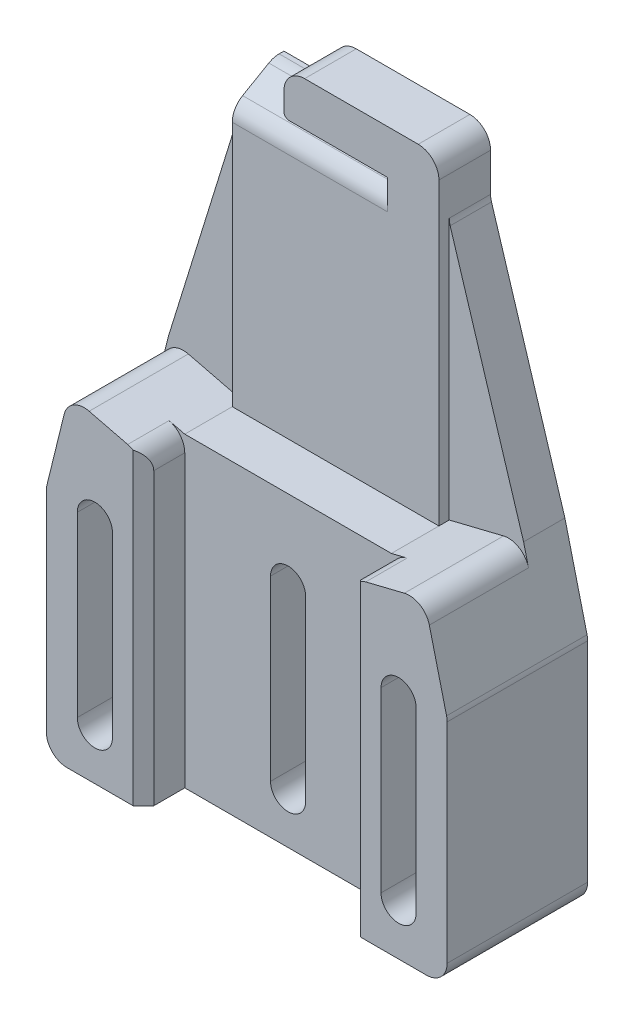
SolidWorks part; units mm, degrees
ref_plane "Front Plane" through (0, 0, 0) normal (0, 0, 1) x (1, 0, 0)
ref_plane "Top Plane" through (0, 0, 0) normal (0, 1, 0) x (1, 0, 0)
ref_plane "Right Plane" through (0, 0, 0) normal (1, 0, 0) x (0, 0, -1)
sketch "Sketch1" plane through (0, 0, 0) normal (0, 0, 1) x (1, 0, 0)
  line L0 (0, 0) -> (10, 0) construction
  line L1 (0, 0) -> (0, 10) construction
  line L2 (16.4, -17.7509) -> (-16.4, -17.7509) construction
  line L3 (16.4, -34.9559) -> (-16.4, -34.9559) construction
  line L4 (-24.9333, -39.6559) -> (24.9333, -39.6559)
  line L5 (-13, -34.9559) -> (-13, -17.7509) construction
  line L6 (-16.4, -17.7509) -> (-16.4, -34.9559) construction
  line L8 (24.9333, -39.6559) -> (10, 21)
  line L9 (10, 21) -> (-10, 21)
  line L10 (-10, 21) -> (-24.9333, -39.6559)
  line L11 (24.9333, -39.6559) -> (-24.9333, -39.6559) construction
  line L12 (-24.9333, -39.6559) -> (-10, 21) construction
  line L13 (10, 21) -> (24.9333, -39.6559) construction
  line L14 (-10, 21) -> (10, 21) construction
  line L18 (5, 15) -> (-5, 15) construction
  line L19 (-5, 16) -> (5, 16) construction
  line L20 (5, 16) -> (5, 15) construction
  line L21 (-5, 15) -> (-5, 16) construction
  line L22 (13, -17.7509) -> (13, -34.9559)
  line L23 (16.4, -34.9559) -> (16.4, -17.7509)
  line L24 (1.7, -17.7509) -> (1.7, -34.9559)
  line L25 (-1.7, -34.9559) -> (-1.7, -17.7509)
  line L26 (-13, -34.9559) -> (-13, -17.7509)
  line L27 (-16.4, -17.7509) -> (-16.4, -34.9559)
  line L29 (-16.4, -34.9559) -> (-16.4, -17.7509)
  line L30 (-13, -17.7509) -> (-13, -34.9559)
  line L31 (16.4, -17.7509) -> (16.4, -34.9559)
  line L32 (13, -34.9559) -> (13, -17.7509)
  line L33 (16.4, -34.9559) -> (16.4, -17.7509) construction
  line L34 (13, -17.7509) -> (13, -34.9559) construction
  line L36 (-1.7, -34.9559) -> (-1.7, -17.7509) construction
  line L37 (1.7, -17.7509) -> (1.7, -34.9559) construction
  line L38 (-5, 16) -> (5, 16) construction
  line L39 (5, 15) -> (-5, 15) construction
  line L40 (5, 16) -> (5, 15) construction
  line L41 (-5, 15) -> (-5, 16) construction
  circle A0 centre (0, 0) radius 10 construction
  circle A1 centre (0, 0) radius 10 construction
  circle A3 centre (0, 72.5) radius 82.5 construction
  arc A13 (16.4, -17.7509) -> (13, -17.7509) centre (14.7, -17.7509) ccw
  arc A14 (13, -34.9559) -> (16.4, -34.9559) centre (14.7, -34.9559) ccw
  arc A15 (-1.7, -34.9559) -> (1.7, -34.9559) centre (0, -34.9559) ccw
  arc A16 (1.7, -17.7509) -> (-1.7, -17.7509) centre (0, -17.7509) ccw
  arc A17 (-16.4, -34.9559) -> (-13, -34.9559) centre (-14.7, -34.9559) ccw
  arc A18 (-13, -17.7509) -> (-16.4, -17.7509) centre (-14.7, -17.7509) ccw
  arc A23 (-13, -34.9559) -> (-16.4, -34.9559) centre (-14.7, -34.9559) cw
  arc A24 (-16.4, -17.7509) -> (-13, -17.7509) centre (-14.7, -17.7509) cw
  arc A25 (13, -17.7509) -> (16.4, -17.7509) centre (14.7, -17.7509) cw
  arc A26 (16.4, -34.9559) -> (13, -34.9559) centre (14.7, -34.9559) cw
  arc A28 (-16.4, -34.9559) -> (-13, -34.9559) centre (-14.7, -34.9559) ccw construction
  arc A29 (13, -34.9559) -> (16.4, -34.9559) centre (14.7, -34.9559) ccw construction
  arc A30 (16.4, -17.7509) -> (13, -17.7509) centre (14.7, -17.7509) ccw construction
  arc A31 (-13, -17.7509) -> (-16.4, -17.7509) centre (-14.7, -17.7509) ccw construction
  arc A32 (1.7, -17.7509) -> (-1.7, -17.7509) centre (0, -17.7509) ccw construction
  arc A33 (-1.7, -34.9559) -> (1.7, -34.9559) centre (0, -34.9559) ccw construction
  circle A34 centre (0, 72.5) radius 82.5 construction
  dimension "D1" = 20
sketch "Sketch2" plane through (0, 0, 0) normal (0, 0, 1) x (1, 0, 0)
  line L0 (10, 21) -> (24.9333, -39.6559) construction
  line L1 (-24.9333, -39.6559) -> (24.9333, -39.6559) construction
  line L2 (-24.9333, -39.6559) -> (-10, 21) construction
  line L3 (-10, 21) -> (10, 21) construction
  line L4 (10, 21) -> (24.9333, -39.6559) construction
  line L5 (24.9333, -39.6559) -> (-24.9333, -39.6559) construction
  line L6 (-24.9333, -39.6559) -> (-10, 21) construction
  line L7 (-10, 21) -> (10, 21)
  line L8 (0, -39.6559) -> (0, 21) construction
  line L9 (10, 21) -> (10, -10) construction
  line L10 (10, -10) -> (-10, -10) construction
  line L11 (-10, -10) -> (-10, 21) construction
  line L12 (10, -10) -> (17.1962, -8.2295) construction
  line L13 (-10, -10) -> (-17.1962, -8.2295) construction
  line L14 (-13, -34.9559) -> (-13, -17.7509) construction
  line L15 (-16.4, -17.7509) -> (-16.4, -34.9559) construction
  line L16 (-19.4, -17.1808) -> (-19.4, -39.6559)
  line L17 (19.4, -17.1808) -> (19.4, -39.6559)
  line L18 (13, -17.7509) -> (13, -34.9559) construction
  line L19 (16.4, -34.9559) -> (16.4, -17.7509) construction
  line L20 (-13, -34.9559) -> (-13, -17.7509) construction
  line L21 (-16.4, -17.7509) -> (-16.4, -34.9559) construction
  line L22 (-1.7, -34.9559) -> (-1.7, -17.7509)
  line L23 (1.7, -17.7509) -> (1.7, -34.9559)
  line L24 (13, -17.7509) -> (13, -34.9559) construction
  line L25 (16.4, -34.9559) -> (16.4, -17.7509) construction
  line L26 (19.4, -39.6559) -> (-19.4, -39.6559)
  line L27 (19.4, -17.1808) -> (10, 21)
  line L28 (-10, 21) -> (-19.4, -17.1808)
  line L30 (-13, -17.7509) -> (-13, -34.9559) construction
  line L31 (-16.4, -34.9559) -> (-16.4, -17.7509) construction
  line L32 (-13, -17.7509) -> (-13, -34.9559) construction
  line L33 (-16.4, -34.9559) -> (-16.4, -17.7509) construction
  line L34 (13, -34.9559) -> (13, -17.7509) construction
  line L35 (16.4, -17.7509) -> (16.4, -34.9559) construction
  line L36 (13, -34.9559) -> (13, -17.7509) construction
  line L37 (16.4, -17.7509) -> (16.4, -34.9559) construction
  line L42 (23.7762, -34.9559) -> (-23.7762, -34.9559) construction
  line L43 (16.4, -34.9559) -> (16.4, -17.7509)
  line L44 (13, -17.7509) -> (13, -34.9559)
  line L45 (-13, -34.9559) -> (-13, -17.7509)
  line L46 (-16.4, -17.7509) -> (-16.4, -34.9559)
  circle A0 centre (0, 0) radius 10 construction
  circle A1 centre (0, 0) radius 10 construction
  circle A2 centre (0, 72.5) radius 82.5 construction
  arc A3 (-16.4, -34.9559) -> (-13, -34.9559) centre (-14.7, -34.9559) ccw construction
  arc A4 (-13, -17.7509) -> (-16.4, -17.7509) centre (-14.7, -17.7509) ccw construction
  arc A5 (1.7, -17.7509) -> (-1.7, -17.7509) centre (0, -17.7509) ccw construction
  arc A7 (13, -34.9559) -> (16.4, -34.9559) centre (14.7, -34.9559) ccw construction
  arc A8 (16.4, -17.7509) -> (13, -17.7509) centre (14.7, -17.7509) ccw construction
  arc A9 (-16.4, -34.9559) -> (-13, -34.9559) centre (-14.7, -34.9559) ccw construction
  arc A10 (-13, -17.7509) -> (-16.4, -17.7509) centre (-14.7, -17.7509) ccw
  arc A11 (1.7, -17.7509) -> (-1.7, -17.7509) centre (0, -17.7509) ccw
  arc A12 (-1.7, -34.9559) -> (1.7, -34.9559) centre (0, -34.9559) ccw
  arc A13 (13, -34.9559) -> (16.4, -34.9559) centre (14.7, -34.9559) ccw
  arc A14 (16.4, -17.7509) -> (13, -17.7509) centre (14.7, -17.7509) ccw construction
  arc A15 (-13, -17.7509) -> (-16.4, -17.7509) centre (-14.7, -17.7509) ccw construction
  arc A16 (-16.4, -34.9559) -> (-13, -34.9559) centre (-14.7, -34.9559) ccw construction
  arc A17 (-13, -17.7509) -> (-16.4, -17.7509) centre (-14.7, -17.7509) ccw construction
  arc A18 (-16.4, -34.9559) -> (-13, -34.9559) centre (-14.7, -34.9559) ccw
  arc A19 (16.4, -17.7509) -> (13, -17.7509) centre (14.7, -17.7509) ccw construction
  arc A20 (13, -34.9559) -> (16.4, -34.9559) centre (14.7, -34.9559) ccw construction
  arc A21 (16.4, -17.7509) -> (13, -17.7509) centre (14.7, -17.7509) ccw
  arc A22 (13, -34.9559) -> (16.4, -34.9559) centre (14.7, -34.9559) ccw construction
  circle A25 centre (-14.7, -34.9559) radius 4.7 construction
sketch "Sketch3" plane through (0, 0, 0) normal (1, 0, 0) x (0, 0, -1)
  line L0 (0, 21) -> (0, -39.6559) construction
  line L1 (0, -39.6559) -> (-13.6002, -39.6559) construction
  line L2 (-13.6002, -39.6559) -> (-13.6002, 21) construction
  line L3 (-13.6002, 21) -> (0, 21) construction
  line L4 (-5, 21) -> (-5, -10)
  line L5 (-5, -10) -> (-9.6002, -10)
  line L6 (-9.6002, -10) -> (-9.6002, -39.6559)
  line L7 (-9.6002, -39.6559) -> (0, -39.6559)
  line L8 (0, -10) -> (-13.6002, -10) construction
  line L11 (-10.7004, -10) -> (-10.7004, 21) construction
  line L12 (-6.6002, -10) -> (-6.6002, 21) construction
  line L13 (-9.1002, -10) -> (-9.1002, 21) construction
  line L14 (-10.7004, 5.5) -> (-9.1002, 5.5) construction
  line L15 (-6.6002, 5.5) -> (-5, 5.5) construction
  line L16 (-7.1002, 21) -> (-7.1002, -10) construction
  line L17 (-5, 21) -> (0, 21)
  line L18 (0, 21) -> (0, -39.6559)
  dimension "D1" = 5
  dimension "D2" = 1.6002
  dimension "D3" = 0.5
  dimension "D4" = 2
  dimension "D5" = 0.5
  dimension "D6" = 4
extrude "Boss-Extrude1" add sketch "Sketch2" along normal up to vertex (13.6002 mm away) up to point (0, 21, 13.6002)
sketch "Sketch4" plane through (0, 0, 13.6002) normal (0, 0, 1) x (1, 0, 0)
  line L0 (-24.9333, -39.6559) -> (-10, 21) construction
  line L1 (-10, 21) -> (10, 21) construction
  line L2 (10, 21) -> (24.9333, -39.6559) construction
  line L3 (-17.1962, -8.2295) -> (-10, 21)
  line L4 (-10, 21) -> (10, 21)
  line L5 (10, 21) -> (17.1962, -8.2295)
  line L6 (10, -10) -> (-10, -10) construction
  line L7 (10, -10) -> (-10, -10)
  line L8 (10, -10) -> (17.1962, -8.2295) construction
  line L9 (10, -10) -> (17.1962, -8.2295)
  line L10 (-10, -10) -> (-17.1962, -8.2295) construction
  line L11 (-10, -10) -> (-17.1962, -8.2295)
extrude "Cut-Extrude1" cut sketch "Sketch4" against normal up to vertex (8.6002 mm away) up to point (0, 21, 5)
sketch "Sketch5" plane through (0, 0, 5) normal (0, 0, 1) x (1, 0, 0)
  line L0 (-10, -10) -> (-17.1962, -8.2295)
  line L1 (-17.1962, -8.2295) -> (-10, 21)
  line L2 (-10, 21) -> (-10, -10)
  line L3 (17.1962, -8.2295) -> (10, -10)
  line L4 (10, -10) -> (10, 21)
  line L5 (10, 21) -> (17.1962, -8.2295)
  line L6 (10, 21) -> (24.9333, -39.6559) construction
  line L7 (10, -10) -> (17.1962, -8.2295) construction
  line L8 (-10, -10) -> (-17.1962, -8.2295) construction
  line L9 (-10, -10) -> (-10, 21) construction
  line L10 (-24.9333, -39.6559) -> (-10, 21) construction
  line L11 (10, 21) -> (10, -10) construction
extrude "Cut-Extrude2" cut sketch "Sketch5" against normal blind 1
sketch "Sketch6" plane through (0, 0, 5) normal (0, 0, 1) x (1, 0, 0)
  line L0 (-17.1962, -8.2295) -> (-10, 21) construction
  line L1 (10, 21) -> (17.1962, -8.2295) construction
  line L2 (-17.1962, -8.2295) -> (-10, 21)
  line L3 (10, 21) -> (17.1962, -8.2295)
  line L4 (10, -10) -> (10, 21) construction
  line L5 (-10, 21) -> (-10, -10) construction
  line L6 (10, 15) -> (10, 21)
  line L7 (-10, 21) -> (-10, 15)
  line L8 (10, 15) -> (-10, 15) construction
  line L9 (5, 15) -> (-5, 15) construction
  line L10 (17.1962, -8.2295) -> (10, 15)
  line L11 (-10, 15) -> (-17.1962, -8.2295)
extrude "Cut-Extrude3" cut sketch "Sketch6" against normal through all
sketch "Sketch7" plane through (0, 0, 13.6002) normal (0, 0, 1) x (1, 0, 0)
  line L0 (24.9333, -39.6559) -> (-24.9333, -39.6559) construction
  line L1 (10, -39.6559) -> (-10, -39.6559)
  line L2 (-10, 21) -> (10, 21) construction
  line L3 (-10, 21) -> (10, 21)
  line L4 (10, 21) -> (10, -39.6559)
  line L5 (-10, 21) -> (-10, -39.6559)
  line L6 (10, 21) -> (10, -10) construction
  line L7 (-10, -10) -> (-10, 21) construction
extrude "Cut-Extrude4" cut sketch "Sketch7" against normal up to vertex (4 mm away) up to point (0, -10, 9.6002)
sketch "Sketch8" plane through (0, 0, 0) normal (1, 0, 0) x (0, 0, -1)
  line L0 (0, 15) -> (-5, 15) construction
  line L1 (0, 21) -> (0, -39.6559) construction
  line L2 (0, 16) -> (-5, 16) construction
  line L3 (-5, 21) -> (-5, -10) construction
  line L4 (-5, 21) -> (0, 21) construction
  line L5 (-5, 21) -> (-5, -10) construction
  line L6 (0, 21) -> (0, -39.6559) construction
  line L7 (-5, 21) -> (0, 21) construction
  line L8 (-5, 15) -> (-1, 17.3094)
  line L9 (-1, 17.3094) -> (0, 17.3094)
  line L10 (-5, 16.1547) -> (0, 19.0415) construction
  line L11 (-4, 16.7321) -> (-5, 16.7321)
  line L12 (0, 19.0415) -> (0, 17.3094)
  line L13 (-4, 16.7321) -> (0, 19.0415)
  line L14 (-5, 15) -> (-5, 16.7321)
  dimension "D1" = 1
  dimension "D2" = 1
  dimension "D3" = 30
extrude "Cut-Extrude5" cut sketch "Sketch8" along normal up to vertex (5 mm away) and the other way through all up to point (5, 15, 0)
sketch "Sketch9" plane through (-10, 0, 0) normal (-1, 0, 0) x (0, 0, 1)
  line L4 (0, 19.0415) -> (4, 16.7321)
  line L5 (5, 16.7321) -> (5, 21)
  line L6 (5, 21) -> (0, 21)
  line L7 (0, 21) -> (0, 19.0415)
  line L8 (0, 19.0415) -> (4, 16.7321)
  line L9 (5, 16.7321) -> (5, 21)
  line L10 (5, 21) -> (0, 21)
  line L11 (0, 21) -> (0, 19.0415)
  line L13 (4, 16.7321) -> (5, 16.7321)
  line L14 (4, 16.7321) -> (5, 16.7321)
  dimension "D1" = 0
extrude "Cut-Extrude6" cut sketch "Sketch9" against normal up to vertex (5 mm away) up to point (-5, 16, 0)
chamfer "Chamfer1" distance 1 angle 45 2 edges at (-10, -24.828, 13.6002) (10, -24.828, 13.6002)
fillet "Fillet1" radius 2 10 edges at (10, 15, 2) (-10, 15, 2) (-5, 21, 2.5) (10, 21, 2.5) (-10, -10, 11.1002) (10, -10, 11.1002) (19.4, -17.1808, 6.8001) (-19.4, -17.1808, 6.8001) (19.4, -39.6559, 6.8001) (-19.4, -39.6559, 6.8001)
fillet "Fillet2" radius 2 3 edges at (-2.5, 15, 5) (0, 16.7321, 4) (-2.5, 17.3094, 1)
fillet "Fillet3" radius 0.5 4 edges at (-4.9999, 19.0207, 0.0359) (-5, 16.7321, 4.7679) (-5, 16.8002, 4.0183) (-5, 18, 1.8038)
sketch "Sketch10" plane through (0, 0, 13.6002) normal (0, 0, 1) x (1, 0, 0)
  line L1 (-17.1962, -8.2295) -> (-11.5222, -9.6255) construction
  line L2 (-17.1962, -8.2295) -> (-17.6742, -10.1712)
  line L3 (-17.1962, -8.2295) -> (-15.2544, -8.7072)
  line L5 (11.5222, -9.6255) -> (17.1962, -8.2295) construction
  line L6 (17.6742, -10.1712) -> (17.1962, -8.2295)
  line L7 (15.2544, -8.7072) -> (17.1962, -8.2295)
  line L8 (-24.9333, -39.6559) -> (-10, 21) construction
  line L9 (10, 21) -> (24.9333, -39.6559) construction
  line L10 (11.5222, -9.6255) -> (17.1962, -8.2295) construction
  arc A0 (17.6742, -10.1712) -> (15.2544, -8.7072) centre (15.7322, -10.6493) ccw
  arc A1 (-15.2544, -8.7072) -> (-17.6742, -10.1712) centre (-15.7322, -10.6493) ccw
  dimension "D1" = 2
extrude "Cut-Extrude7" cut sketch "Sketch10" against normal up to surface (9.6002 mm away) up to face at (11.8159, 2.9452, 4)
